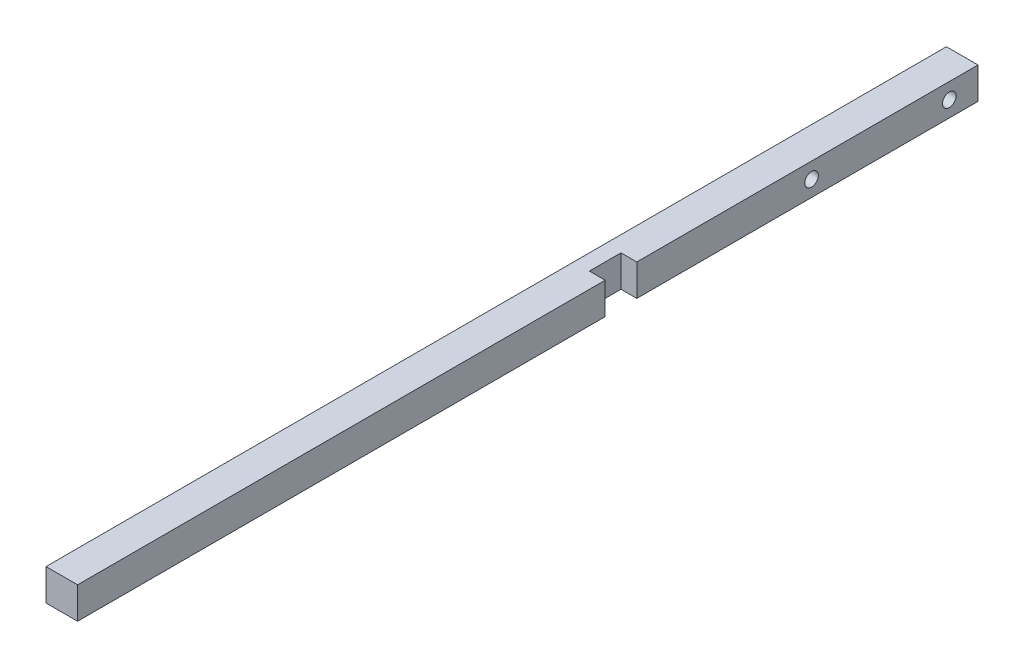
SolidWorks part; units mm, degrees
ref_plane "Plan de face" through (0, 0, 0) normal (0, 0, 1) x (1, 0, 0)
ref_plane "Plan de dessus" through (0, 0, 0) normal (0, 1, 0) x (1, 0, 0)
ref_plane "Plan de droite" through (0, 0, 0) normal (1, 0, 0) x (0, 0, -1)
sketch "Esquisse1" plane through (0, 0, 0) normal (0, 0, 1) x (1, 0, 0)
  line L0 (-5, 5) -> (5, -5) construction
  line L1 (-5, 5) -> (5, 5)
  line L2 (-5, 5) -> (-5, -5)
  line L3 (-5, -5) -> (5, -5)
  line L4 (5, 5) -> (5, -5)
  dimension "D1" = 10
extrude "Boss.-Extru.1" add sketch "Esquisse1" along normal offset from surface (307 mm away) 2 offset beyond the face yes
sketch "Esquisse2" plane through (0, 0, 0) normal (0, 1, 0) x (1, 0, 0)
  line L0 (-5, 0) -> (-5, -22)
  line L2 (-5, -22) -> (5, -22)
  line L3 (5, -22) -> (5, 0)
  line L4 (5, 0) -> (-5, 0)
  line L5 (-5, -307) -> (-5, 0) construction
  line L6 (5, -307) -> (5, 0) construction
  line L10 (-24, -22) -> (-60, -22) construction
extrude "Enlèv. mat.-Extru.1" cut sketch "Esquisse2" against normal through all and the other way through all
sketch "Esquisse3" plane through (0, -5, 0) normal (0, -1, 0) x (1, 0, 0)
  line L0 (-5, 140) -> (0, 140) construction
  line L1 (0, 130) -> (5, 130)
  line L2 (0, 130) -> (0, 140)
  line L3 (0, 140) -> (5, 140)
  line L4 (5, 130) -> (5, 140)
  line L5 (5, 307) -> (5, 22) construction
extrude "Enlèv. mat.-Extru.2" cut sketch "Esquisse3" against normal through all
hole_wizard "Dégagement M41" positions "Esquisse5" profile "Esquisse4" hole size "M4" standard "Ansi Metric" end condition through all
sketch "Esquisse5" plane through (-5, 0, 0) normal (-1, 0, 0) x (0, 0, 1)
  point P0 (74.69, 0)
  point P3 (31.09, 0)
sketch "Esquisse4" plane through (-5, 0, 74.69) normal (0, 1, 0) x (0, 0, 1)
  line L0 (0, 0) -> (0, 10)
  line L1 (0, 10) -> (2.15, 10)
  line L2 (2.15, 10) -> (2.15, 0)
  line L5 (2.15, 0) -> (0, 0)
  line L11 (0, -6.35) -> (0, 107.95) construction
  dimension "Diamètre du perçage jusqu'au prochain" = 4.3
  dimension "Profondeur du perçage jusqu'au prochain" = 10
